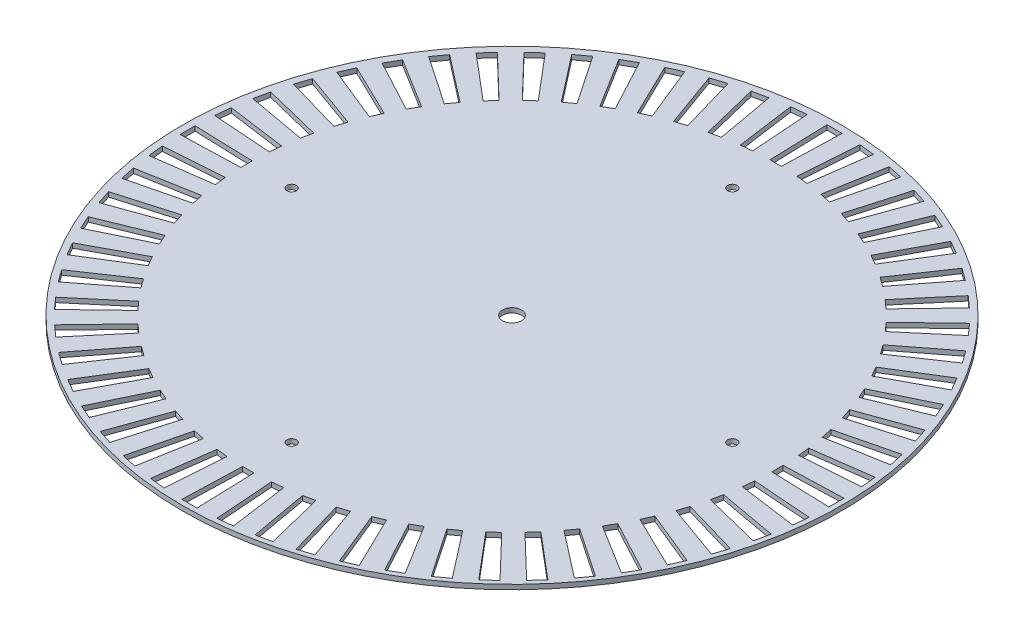
SolidWorks part; units mm, degrees
ref_plane "Front Plane" through (0, 0, 0) normal (0, 0, 1) x (1, 0, 0)
ref_plane "Top Plane" through (0, 0, 0) normal (0, 1, 0) x (1, 0, 0)
ref_plane "Right Plane" through (0, 0, 0) normal (1, 0, 0) x (0, 0, -1)
sketch "Sketch1" plane through (0, 0, 0) normal (0, 1, 0) x (1, 0, 0)
  circle A0 centre (0, 0) radius 1
  circle A1 centre (0, 0) radius 35
extrude "Boss-Extrude2" add sketch "Sketch1" along normal blind 0.5
sketch "Sketch2" plane through (0, 0.5, 0) normal (0, 1, 0) x (1, 0, 0)
  line L0 (0, 0) -> (0, 32.1339) construction
  line L1 (-0.8, 34.2549) -> (0.8, 34.2549)
  line L2 (0.8, 34.2549) -> (0.6, 28.0001)
  line L3 (0.6, 28.0001) -> (-0.6, 28.0001)
  line L4 (0, 34.0001) -> (10.071, 34.0001) construction
  line L5 (-0.8, 34.2549) -> (-0.6, 28.0001)
  line L6 (2.796, 34.1607) -> (4.3872, 33.9935)
  line L7 (4.3872, 33.9935) -> (3.5345, 27.7939)
  line L8 (3.5345, 27.7939) -> (2.3411, 27.9193)
  line L9 (2.796, 34.1607) -> (2.3411, 27.9193)
  line L10 (6.3624, 33.6912) -> (7.9275, 33.3586)
  line L11 (7.9275, 33.3586) -> (6.4314, 27.282)
  line L12 (6.4314, 27.282) -> (5.2576, 27.5315)
  line L13 (6.3624, 33.6912) -> (5.2576, 27.5315)
  line L14 (9.8603, 32.8515) -> (11.382, 32.3571)
  line L15 (11.382, 32.3571) -> (9.2589, 26.4702)
  line L16 (9.2589, 26.4702) -> (8.1177, 26.8411)
  line L17 (9.8603, 32.8515) -> (8.1177, 26.8411)
  line L18 (13.2512, 31.6508) -> (14.7129, 31)
  line L19 (14.7129, 31) -> (11.9861, 25.3673)
  line L20 (11.9861, 25.3673) -> (10.8898, 25.8554)
  line L21 (13.2512, 31.6508) -> (10.8898, 25.8554)
  line L22 (16.498, 30.1022) -> (17.8836, 29.3022)
  line L23 (17.8836, 29.3022) -> (14.583, 23.9854)
  line L24 (14.583, 23.9854) -> (13.5438, 24.5854)
  line L25 (16.498, 30.1022) -> (13.5438, 24.5854)
  line L26 (19.5652, 28.2227) -> (20.8596, 27.2822)
  line L27 (20.8596, 27.2822) -> (17.0213, 22.3395)
  line L28 (17.0213, 22.3395) -> (16.0505, 23.0449)
  line L29 (19.5652, 28.2227) -> (16.0505, 23.0449)
  line L30 (22.4191, 26.0329) -> (23.6081, 24.9622)
  line L31 (23.6081, 24.9622) -> (19.2742, 20.4478)
  line L32 (19.2742, 20.4478) -> (18.3824, 21.2508)
  line L33 (22.4191, 26.0329) -> (18.3824, 21.2508)
  line L34 (25.0284, 23.5567) -> (26.099, 22.3677)
  line L35 (26.099, 22.3677) -> (21.317, 18.331)
  line L36 (21.317, 18.331) -> (20.514, 19.2228)
  line L37 (25.0284, 23.5567) -> (20.514, 19.2228)
  line L38 (27.3647, 20.8214) -> (28.3051, 19.527)
  line L39 (28.3051, 19.527) -> (23.1273, 16.0123)
  line L40 (23.1273, 16.0123) -> (22.422, 16.9831)
  line L41 (27.3647, 20.8214) -> (22.422, 16.9831)
  line L42 (29.4022, 17.8569) -> (30.2022, 16.4712)
  line L43 (30.2022, 16.4712) -> (24.6854, 13.517)
  line L44 (24.6854, 13.517) -> (24.0854, 14.5562)
  line L45 (29.4022, 17.8569) -> (24.0854, 14.5562)
  line L46 (31.1187, 14.6956) -> (31.7694, 13.2339)
  line L47 (31.7694, 13.2339) -> (25.974, 10.8726)
  line L48 (25.974, 10.8726) -> (25.486, 11.9688)
  line L49 (31.1187, 14.6956) -> (25.486, 11.9688)
  line L50 (32.4953, 11.3722) -> (32.9897, 9.8505)
  line L51 (32.9897, 9.8505) -> (26.9793, 8.1079)
  line L52 (26.9793, 8.1079) -> (26.6084, 9.2491)
  line L53 (32.4953, 11.3722) -> (26.6084, 9.2491)
  line L54 (33.517, 7.9231) -> (33.8497, 6.3581)
  line L55 (33.8497, 6.3581) -> (27.69, 5.2533)
  line L56 (27.69, 5.2533) -> (27.4405, 6.427)
  line L57 (33.517, 7.9231) -> (27.4405, 6.427)
  line L58 (34.1726, 4.3861) -> (34.3398, 2.7949)
  line L59 (34.3398, 2.7949) -> (28.0984, 2.34)
  line L60 (28.0984, 2.34) -> (27.973, 3.5334)
  line L61 (34.1726, 4.3861) -> (27.973, 3.5334)
  line L62 (34.4549, 0.8) -> (34.4549, -0.8)
  line L63 (34.4549, -0.8) -> (28.2001, -0.6)
  line L64 (28.2001, -0.6) -> (28.2001, 0.6)
  line L65 (34.4549, 0.8) -> (28.2001, 0.6)
  line L66 (34.3607, -2.796) -> (34.1935, -4.3872)
  line L67 (34.1935, -4.3872) -> (27.9939, -3.5345)
  line L68 (27.9939, -3.5345) -> (28.1193, -2.3411)
  line L69 (34.3607, -2.796) -> (28.1193, -2.3411)
  line L70 (33.8912, -6.3624) -> (33.5586, -7.9275)
  line L71 (33.5586, -7.9275) -> (27.482, -6.4314)
  line L72 (27.482, -6.4314) -> (27.7315, -5.2576)
  line L73 (33.8912, -6.3624) -> (27.7315, -5.2576)
  line L74 (33.0515, -9.8603) -> (32.5571, -11.382)
  line L75 (32.5571, -11.382) -> (26.6702, -9.2589)
  line L76 (26.6702, -9.2589) -> (27.0411, -8.1177)
  line L77 (33.0515, -9.8603) -> (27.0411, -8.1177)
  line L78 (31.8508, -13.2512) -> (31.2, -14.7129)
  line L79 (31.2, -14.7129) -> (25.5673, -11.9861)
  line L80 (25.5673, -11.9861) -> (26.0554, -10.8898)
  line L81 (31.8508, -13.2512) -> (26.0554, -10.8898)
  line L82 (30.3022, -16.498) -> (29.5022, -17.8836)
  line L83 (29.5022, -17.8836) -> (24.1854, -14.583)
  line L84 (24.1854, -14.583) -> (24.7854, -13.5438)
  line L85 (30.3022, -16.498) -> (24.7854, -13.5438)
  line L86 (28.4227, -19.5652) -> (27.4822, -20.8596)
  line L87 (27.4822, -20.8596) -> (22.5395, -17.0213)
  line L88 (22.5395, -17.0213) -> (23.2449, -16.0505)
  line L89 (28.4227, -19.5652) -> (23.2449, -16.0505)
  line L90 (26.2329, -22.4191) -> (25.1622, -23.6081)
  line L91 (25.1622, -23.6081) -> (20.6478, -19.2742)
  line L92 (20.6478, -19.2742) -> (21.4508, -18.3824)
  line L93 (26.2329, -22.4191) -> (21.4508, -18.3824)
  line L94 (23.7567, -25.0284) -> (22.5677, -26.099)
  line L95 (22.5677, -26.099) -> (18.531, -21.317)
  line L96 (18.531, -21.317) -> (19.4228, -20.514)
  line L97 (23.7567, -25.0284) -> (19.4228, -20.514)
  line L98 (21.0214, -27.3647) -> (19.727, -28.3051)
  line L99 (19.727, -28.3051) -> (16.2123, -23.1273)
  line L100 (16.2123, -23.1273) -> (17.1831, -22.422)
  line L101 (21.0214, -27.3647) -> (17.1831, -22.422)
  line L102 (18.0569, -29.4022) -> (16.6712, -30.2022)
  line L103 (16.6712, -30.2022) -> (13.717, -24.6854)
  line L104 (13.717, -24.6854) -> (14.7562, -24.0854)
  line L105 (18.0569, -29.4022) -> (14.7562, -24.0854)
  line L106 (14.8956, -31.1187) -> (13.4339, -31.7694)
  line L107 (13.4339, -31.7694) -> (11.0726, -25.974)
  line L108 (11.0726, -25.974) -> (12.1688, -25.486)
  line L109 (14.8956, -31.1187) -> (12.1688, -25.486)
  line L110 (11.5722, -32.4953) -> (10.0505, -32.9897)
  line L111 (10.0505, -32.9897) -> (8.3079, -26.9793)
  line L112 (8.3079, -26.9793) -> (9.4491, -26.6084)
  line L113 (11.5722, -32.4953) -> (9.4491, -26.6084)
  line L114 (8.1231, -33.517) -> (6.5581, -33.8497)
  line L115 (6.5581, -33.8497) -> (5.4533, -27.69)
  line L116 (5.4533, -27.69) -> (6.627, -27.4405)
  line L117 (8.1231, -33.517) -> (6.627, -27.4405)
  line L118 (4.5861, -34.1726) -> (2.9949, -34.3398)
  line L119 (2.9949, -34.3398) -> (2.54, -28.0984)
  line L120 (2.54, -28.0984) -> (3.7334, -27.973)
  line L121 (4.5861, -34.1726) -> (3.7334, -27.973)
  line L122 (1, -34.4549) -> (-0.6, -34.4549)
  line L123 (-0.6, -34.4549) -> (-0.4, -28.2001)
  line L124 (-0.4, -28.2001) -> (0.8, -28.2001)
  line L125 (1, -34.4549) -> (0.8, -28.2001)
  line L126 (-2.596, -34.3607) -> (-4.1872, -34.1935)
  line L127 (-4.1872, -34.1935) -> (-3.3345, -27.9939)
  line L128 (-3.3345, -27.9939) -> (-2.1411, -28.1193)
  line L129 (-2.596, -34.3607) -> (-2.1411, -28.1193)
  line L130 (-6.1624, -33.8912) -> (-7.7275, -33.5586)
  line L131 (-7.7275, -33.5586) -> (-6.2314, -27.482)
  line L132 (-6.2314, -27.482) -> (-5.0576, -27.7315)
  line L133 (-6.1624, -33.8912) -> (-5.0576, -27.7315)
  line L134 (-9.6603, -33.0515) -> (-11.182, -32.5571)
  line L135 (-11.182, -32.5571) -> (-9.0589, -26.6702)
  line L136 (-9.0589, -26.6702) -> (-7.9177, -27.0411)
  line L137 (-9.6603, -33.0515) -> (-7.9177, -27.0411)
  line L138 (-13.0512, -31.8508) -> (-14.5129, -31.2)
  line L139 (-14.5129, -31.2) -> (-11.7861, -25.5673)
  line L140 (-11.7861, -25.5673) -> (-10.6898, -26.0554)
  line L141 (-13.0512, -31.8508) -> (-10.6898, -26.0554)
  line L142 (-16.298, -30.3022) -> (-17.6836, -29.5022)
  line L143 (-17.6836, -29.5022) -> (-14.383, -24.1854)
  line L144 (-14.383, -24.1854) -> (-13.3438, -24.7854)
  line L145 (-16.298, -30.3022) -> (-13.3438, -24.7854)
  line L146 (-19.3652, -28.4227) -> (-20.6596, -27.4822)
  line L147 (-20.6596, -27.4822) -> (-16.8213, -22.5395)
  line L148 (-16.8213, -22.5395) -> (-15.8505, -23.2449)
  line L149 (-19.3652, -28.4227) -> (-15.8505, -23.2449)
  line L150 (-22.2191, -26.2329) -> (-23.4081, -25.1622)
  line L151 (-23.4081, -25.1622) -> (-19.0742, -20.6478)
  line L152 (-19.0742, -20.6478) -> (-18.1824, -21.4508)
  line L153 (-22.2191, -26.2329) -> (-18.1824, -21.4508)
  line L154 (-24.8284, -23.7567) -> (-25.899, -22.5677)
  line L155 (-25.899, -22.5677) -> (-21.117, -18.531)
  line L156 (-21.117, -18.531) -> (-20.314, -19.4228)
  line L157 (-24.8284, -23.7567) -> (-20.314, -19.4228)
  line L158 (-27.1647, -21.0214) -> (-28.1051, -19.727)
  line L159 (-28.1051, -19.727) -> (-22.9273, -16.2123)
  line L160 (-22.9273, -16.2123) -> (-22.222, -17.1831)
  line L161 (-27.1647, -21.0214) -> (-22.222, -17.1831)
  line L162 (-29.2022, -18.0569) -> (-30.0022, -16.6712)
  line L163 (-30.0022, -16.6712) -> (-24.4854, -13.717)
  line L164 (-24.4854, -13.717) -> (-23.8854, -14.7562)
  line L165 (-29.2022, -18.0569) -> (-23.8854, -14.7562)
  line L166 (-30.9187, -14.8956) -> (-31.5694, -13.4339)
  line L167 (-31.5694, -13.4339) -> (-25.774, -11.0726)
  line L168 (-25.774, -11.0726) -> (-25.286, -12.1688)
  line L169 (-30.9187, -14.8956) -> (-25.286, -12.1688)
  line L170 (-32.2953, -11.5722) -> (-32.7897, -10.0505)
  line L171 (-32.7897, -10.0505) -> (-26.7793, -8.3079)
  line L172 (-26.7793, -8.3079) -> (-26.4084, -9.4491)
  line L173 (-32.2953, -11.5722) -> (-26.4084, -9.4491)
  line L174 (-33.317, -8.1231) -> (-33.6497, -6.5581)
  line L175 (-33.6497, -6.5581) -> (-27.49, -5.4533)
  line L176 (-27.49, -5.4533) -> (-27.2405, -6.627)
  line L177 (-33.317, -8.1231) -> (-27.2405, -6.627)
  line L178 (-33.9726, -4.5861) -> (-34.1398, -2.9949)
  line L179 (-34.1398, -2.9949) -> (-27.8984, -2.54)
  line L180 (-27.8984, -2.54) -> (-27.773, -3.7334)
  line L181 (-33.9726, -4.5861) -> (-27.773, -3.7334)
  line L182 (-34.2549, -1) -> (-34.2549, 0.6)
  line L183 (-34.2549, 0.6) -> (-28.0001, 0.4)
  line L184 (-28.0001, 0.4) -> (-28.0001, -0.8)
  line L185 (-34.2549, -1) -> (-28.0001, -0.8)
  line L186 (-34.1607, 2.596) -> (-33.9935, 4.1872)
  line L187 (-33.9935, 4.1872) -> (-27.7939, 3.3345)
  line L188 (-27.7939, 3.3345) -> (-27.9193, 2.1411)
  line L189 (-34.1607, 2.596) -> (-27.9193, 2.1411)
  line L190 (-33.6912, 6.1624) -> (-33.3586, 7.7275)
  line L191 (-33.3586, 7.7275) -> (-27.282, 6.2314)
  line L192 (-27.282, 6.2314) -> (-27.5315, 5.0576)
  line L193 (-33.6912, 6.1624) -> (-27.5315, 5.0576)
  line L194 (-32.8515, 9.6603) -> (-32.3571, 11.182)
  line L195 (-32.3571, 11.182) -> (-26.4702, 9.0589)
  line L196 (-26.4702, 9.0589) -> (-26.8411, 7.9177)
  line L197 (-32.8515, 9.6603) -> (-26.8411, 7.9177)
  line L198 (-31.6508, 13.0512) -> (-31, 14.5129)
  line L199 (-31, 14.5129) -> (-25.3673, 11.7861)
  line L200 (-25.3673, 11.7861) -> (-25.8554, 10.6898)
  line L201 (-31.6508, 13.0512) -> (-25.8554, 10.6898)
  line L202 (-30.1022, 16.298) -> (-29.3022, 17.6836)
  line L203 (-29.3022, 17.6836) -> (-23.9854, 14.383)
  line L204 (-23.9854, 14.383) -> (-24.5854, 13.3438)
  line L205 (-30.1022, 16.298) -> (-24.5854, 13.3438)
  line L206 (-28.2227, 19.3652) -> (-27.2822, 20.6596)
  line L207 (-27.2822, 20.6596) -> (-22.3395, 16.8213)
  line L208 (-22.3395, 16.8213) -> (-23.0449, 15.8505)
  line L209 (-28.2227, 19.3652) -> (-23.0449, 15.8505)
  line L210 (-26.0329, 22.2191) -> (-24.9622, 23.4081)
  line L211 (-24.9622, 23.4081) -> (-20.4478, 19.0742)
  line L212 (-20.4478, 19.0742) -> (-21.2508, 18.1824)
  line L213 (-26.0329, 22.2191) -> (-21.2508, 18.1824)
  line L214 (-23.5567, 24.8284) -> (-22.3677, 25.899)
  line L215 (-22.3677, 25.899) -> (-18.331, 21.117)
  line L216 (-18.331, 21.117) -> (-19.2228, 20.314)
  line L217 (-23.5567, 24.8284) -> (-19.2228, 20.314)
  line L218 (-20.8214, 27.1647) -> (-19.527, 28.1051)
  line L219 (-19.527, 28.1051) -> (-16.0123, 22.9273)
  line L220 (-16.0123, 22.9273) -> (-16.9831, 22.222)
  line L221 (-20.8214, 27.1647) -> (-16.9831, 22.222)
  line L222 (-17.8569, 29.2022) -> (-16.4712, 30.0022)
  line L223 (-16.4712, 30.0022) -> (-13.517, 24.4854)
  line L224 (-13.517, 24.4854) -> (-14.5562, 23.8854)
  line L225 (-17.8569, 29.2022) -> (-14.5562, 23.8854)
  line L226 (-14.6956, 30.9187) -> (-13.2339, 31.5694)
  line L227 (-13.2339, 31.5694) -> (-10.8726, 25.774)
  line L228 (-10.8726, 25.774) -> (-11.9688, 25.286)
  line L229 (-14.6956, 30.9187) -> (-11.9688, 25.286)
  line L230 (-11.3722, 32.2953) -> (-9.8505, 32.7897)
  line L231 (-9.8505, 32.7897) -> (-8.1079, 26.7793)
  line L232 (-8.1079, 26.7793) -> (-9.2491, 26.4084)
  line L233 (-11.3722, 32.2953) -> (-9.2491, 26.4084)
  line L234 (-7.9231, 33.317) -> (-6.3581, 33.6497)
  line L235 (-6.3581, 33.6497) -> (-5.2533, 27.49)
  line L236 (-5.2533, 27.49) -> (-6.427, 27.2405)
  line L237 (-7.9231, 33.317) -> (-6.427, 27.2405)
  line L238 (-4.3861, 33.9726) -> (-2.7949, 34.1398)
  line L239 (-2.7949, 34.1398) -> (-2.34, 27.8984)
  line L240 (-2.34, 27.8984) -> (-3.5334, 27.773)
  line L241 (-4.3861, 33.9726) -> (-3.5334, 27.773)
  circle A0 centre (0, 23.3998) radius 0.5
  circle A1 centre (23.3998, 0) radius 0.5
  circle A2 centre (0, -23.3998) radius 0.5
  circle A3 centre (-23.3998, 0) radius 0.5
  point P207 (0.1, -0.1)
  point P256 (0, 0)
  dimension "D5" = 23.5
  dimension "D1" = 6
  dimension "D2" = 1.6
  dimension "D3" = 1.2
  dimension "D4" = 60
  dimension "D6" = 4
extrude "Cut-Extrude1" cut sketch "Sketch2" against normal blind 0.5
